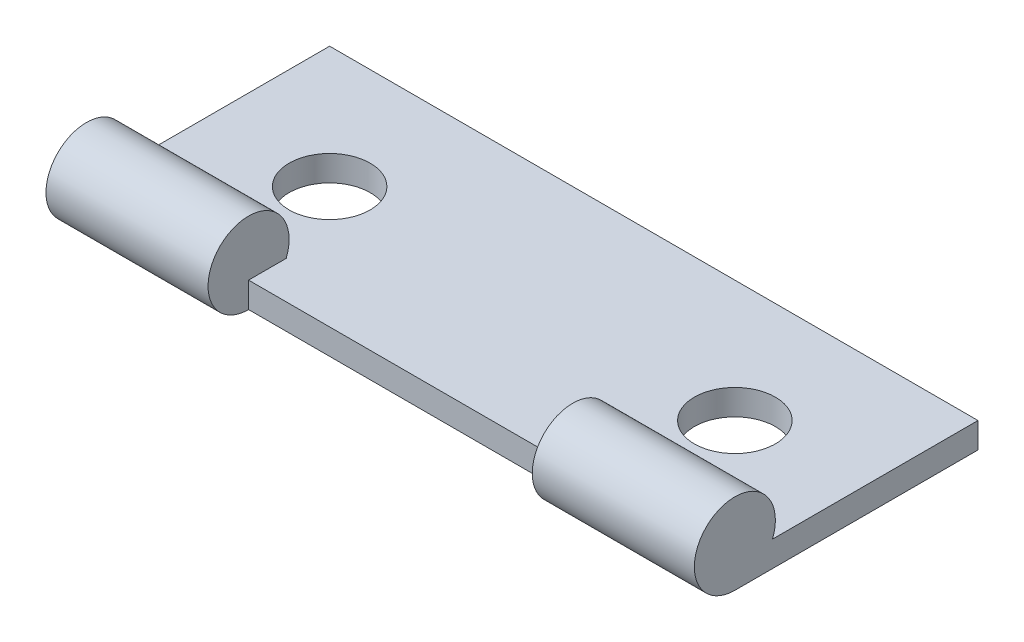
SolidWorks part; units mm, degrees
ref_plane "Front Plane" through (0, 0, 0) normal (0, 0, 1) x (1, 0, 0)
ref_plane "Top Plane" through (0, 0, 0) normal (0, 1, 0) x (1, 0, 0)
ref_plane "Right Plane" through (0, 0, 0) normal (1, 0, 0) x (0, 0, -1)
sketch "Sketch1" plane through (0, 0, 0) normal (0, 1, 0) x (1, 0, 0)
  line L0 (12.7, 9.525) -> (12.7, 0) construction
  line L1 (0, 0) -> (25.4, 0)
  line L2 (0, 0) -> (0, 9.525)
  line L3 (0, 9.525) -> (25.4, 9.525)
  line L4 (25.4, 0) -> (25.4, 9.525)
  circle A0 centre (4.7625, 4.7625) radius 1.5875
  circle A1 centre (20.6375, 4.7625) radius 1.5875
  dimension "D3" = 3.175
  dimension "D1" = 9.525
  dimension "D2" = 25.4
  dimension "D4" = 4.7625
  dimension "D5" = 4.7625
extrude "Boss-Extrude1" add sketch "Sketch1" along normal blind 1
sketch "Sketch2" plane through (0, 0, 0) normal (-1, 0, 0) x (0, 0, 1)
  line L0 (0, 0) -> (0, 1.5875) construction
  line L1 (0, 1) -> (0, 0) construction
  circle A0 centre (0, 1.5875) radius 1.5875
  dimension "D1" = 1.5875
extrude "Boss-Extrude2" add sketch "Sketch2" against normal blind 6.35
pattern_linear "LPattern1" count 2 spacing 19.05 along (1, 0, 0) of "Boss-Extrude2"
